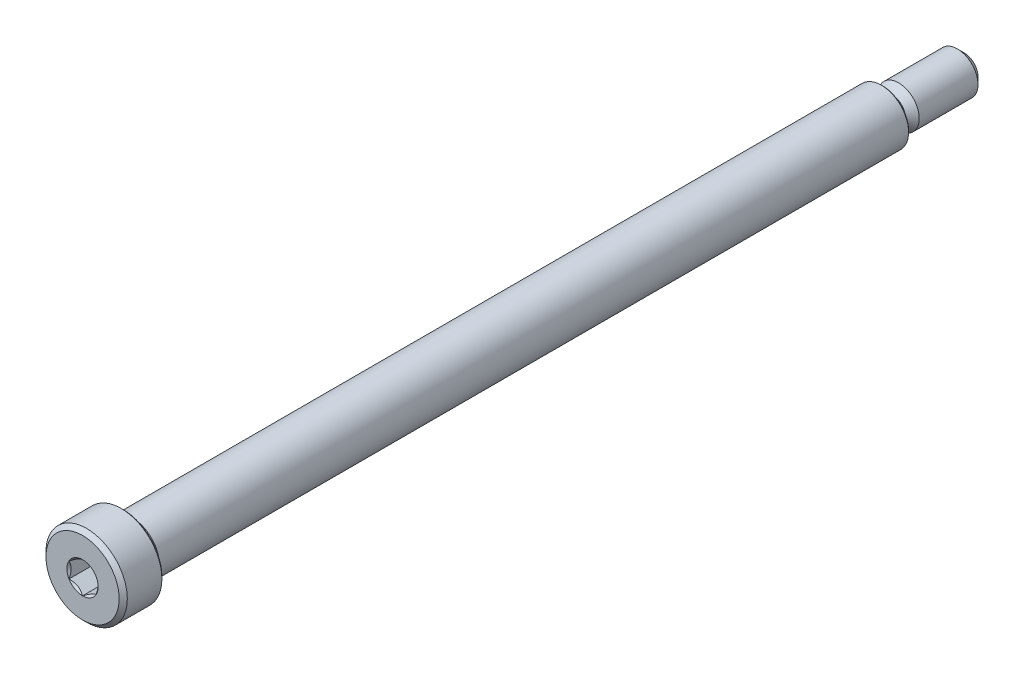
SolidWorks part; units mm, degrees
ref_plane "Front Plane" through (0, 0, 0) normal (0, 0, 1) x (1, 0, 0)
ref_plane "Top Plane" through (0, 0, 0) normal (0, 1, 0) x (1, 0, 0)
ref_plane "Right Plane" through (0, 0, 0) normal (1, 0, 0) x (0, 0, -1)
sketch "Sketch1" plane through (0, 0, 0) normal (0, 0, 1) x (1, 0, 0)
  line L1 (0, 1.8331) -> (-1.5875, 0.9165)
  line L2 (-1.5875, 0.9165) -> (-1.5875, -0.9165)
  line L3 (-1.5875, -0.9165) -> (0, -1.8331)
  line L4 (0, -1.8331) -> (1.5875, -0.9165)
  line L5 (1.5875, -0.9165) -> (1.5875, 0.9165)
  line L6 (1.5875, 0.9165) -> (0, 1.8331)
  circle A0 centre (0, 0) radius 4.7625
  circle A1 centre (0, 0) radius 1.5875 construction
  point P3 (0, 4.7625)
  point P11 (0, -4.7625)
  dimension "Head Diameter" = 9.525
  dimension "Drive Size" = 3.175
sketch "Sketch2" plane through (0, 0, 0) normal (1, 0, 0) x (0, 0, -1)
  line L0 (-51.5937, 0) -> (51.5938, 0) construction
  point P2 (0, 0)
  point P4 (-46.8312, 0)
  point P5 (42.0687, 0)
  point P6 (-46.8312, -3.175)
  point P7 (-48.4981, 0)
  point P8 (50.5354, 0)
  point P9 (50.0062, -2.413)
  point P10 (51.5938, 2.413)
  point P12 (51.5938, -2.413)
  point P15 (-45.7729, -3.175)
  dimension "Head Height" = 4.7625
  dimension "Shoulder Length" = 88.9
  dimension "Thread Length" = 9.525
  dimension "Screw Size Decimal Equivalent" = 4.826
  dimension "Thread Pitch" = 1.0583
  dimension "D1" = 3.0956
  dimension "D2" = 1.5875
  dimension "D3" = 1.0583
  dimension "Shoulder Diameter" = 6.35
sketch "Sketch3" plane through (0, 0, 0) normal (1, 0, 0) x (0, 0, -1)
  line L0 (-51.5937, 0) -> (-51.5937, 4.2862)
  line L1 (-51.1175, 4.7625) -> (-47.0694, 4.7625)
  line L2 (-46.8312, 4.5244) -> (-46.8312, 3.1353)
  line L3 (-46.7122, 3.0162) -> (-45.9317, 3.0162)
  line L4 (-45.7729, 3.0162) -> (-45.7729, 3.175) construction
  line L5 (-45.7729, 3.175) -> (41.91, 3.175)
  line L6 (42.4656, 1.6192) -> (42.4656, 2.413) construction
  line L7 (-51.5937, 0) -> (51.5938, 0)
  line L8 (42.0687, 3.0163) -> (42.0687, 2.0161)
  line L9 (42.4656, 1.6192) -> (43.1271, 1.6192)
  line L10 (43.1271, 1.6192) -> (43.9208, 2.413)
  line L11 (43.9208, 2.413) -> (50.8, 2.413)
  line L12 (50.8, 2.413) -> (51.5938, 1.6192)
  line L13 (51.5938, 1.6192) -> (51.5938, 0)
  line L14 (-51.5937, 4.2862) -> (-51.1175, 4.7625)
  line L15 (-47.0694, 4.7625) -> (-46.8312, 4.5244)
  line L16 (-51.1175, 4.7625) -> (-51.1175, 4.5244) construction
  line L17 (-51.1175, 4.5244) -> (-51.1175, 4.2862) construction
  line L18 (-46.7122, 3.0162) -> (-46.7122, 3.0559) construction
  line L19 (-46.7122, 3.0559) -> (-46.7122, 3.0956) construction
  line L20 (-46.7122, 3.0956) -> (-46.7122, 3.1353) construction
  line L21 (-46.7122, 3.1353) -> (-46.7122, 3.175) construction
  line L22 (-45.7729, 3.175) -> (-45.9317, 3.0162)
  line L23 (41.91, 3.175) -> (42.0687, 3.0163)
  arc A0 (-46.8312, 3.1353) -> (-46.7122, 3.0162) centre (-46.7122, 3.1353) ccw
  arc A1 (42.0687, 2.0161) -> (42.4656, 1.6192) centre (42.4656, 2.0161) ccw
  point P3 (-50.8794, 4.7625)
  point P11 (-48.9744, 4.7625)
  point P35 (42.4656, 2.0161)
  dimension "D1" = 3.175
  dimension "D2" = 3.0162
  dimension "D5" = 2.413
  dimension "D6" = 45
  dimension "D7" = 0.7938
  dimension "D8" = 0.4763
  dimension "D4" = 1.0583
  dimension "D9" = 0.2381
  dimension "D10" = 1.905
revolve "Revolve1" add sketch "Sketch3" angle 360 about L7
sketch "Sketch4" plane through (0, 0, 51.5937) normal (0, 0, 1) x (1, 0, 0)
  line L0 (-1.5875, -0.9165) -> (0, -1.8331) construction
  line L1 (-1.5875, 0.9165) -> (-1.5875, -0.9165) construction
  line L2 (0, 1.8331) -> (-1.5875, 0.9165) construction
  line L3 (1.5875, 0.9165) -> (0, 1.8331) construction
  line L4 (1.5875, -0.9165) -> (1.5875, 0.9165) construction
  line L5 (0, -1.8331) -> (1.5875, -0.9165) construction
  line L6 (-1.5875, -0.9165) -> (0, -1.8331)
  line L7 (-1.5875, 0.9165) -> (-1.5875, -0.9165)
  line L8 (0, 1.8331) -> (-1.5875, 0.9165)
  line L9 (1.5875, 0.9165) -> (0, 1.8331)
  line L10 (1.5875, -0.9165) -> (1.5875, 0.9165)
  line L11 (0, -1.8331) -> (1.5875, -0.9165)
extrude "Cut-Extrude1" cut sketch "Sketch4" against normal up to vertex (3.0956 mm away) up to point (0, 0, 48.4981)
sketch "Sketch5" plane through (0, 0, 51.5937) normal (0, 0, 1) x (1, 0, 0)
  circle A0 centre (0, 0) radius 1.8331
extrude "Cut-Extrude2" cut sketch "Sketch5" against normal up to vertex (3.0956 mm away) draft 45 up to point (0, 0, 48.4981)
ref_plane "Plane1" [suppressed] through (0, 0, -43.1271) normal (0, 0, 1) x (1, 0, 0)
split "Split1" [suppressed] bodies to split 106
sketch "Sketch6" [suppressed] plane through (0, 0, -51.5938) normal (0, 0, -1) x (-1, 0, 0)
  circle A0 centre (0, 0) radius 2.413 construction
  circle A1 centre (0, 0) radius 2.413
curve "Helix/Spiral1" [suppressed] pitch 1.0583 height 9.525 turns 9
sketch "Sketch7" [suppressed] plane through (0, 0, 0) normal (1, 0, 0) x (0, 0, -1)
  line L0 (51.5276, 2.5276) -> (52.0568, 1.611) construction
  line L1 (52.0568, 1.611) -> (52.5859, 2.5276) construction
  line L2 (52.5859, 2.5276) -> (51.5276, 2.5276) construction
  line L3 (51.5607, 2.4703) -> (52.5529, 2.4703)
  line L4 (52.5529, 2.4703) -> (52.1229, 1.7256)
  line L5 (52.1229, 1.7256) -> (51.9906, 1.7256)
  line L6 (51.9906, 1.7256) -> (51.5607, 2.4703)
  line L7 (52.0568, 1.7256) -> (52.0568, 1.611) construction
  line L8 (51.5938, 2.413) -> (52.5198, 2.413) construction
  line L9 (52.0568, 2.5276) -> (52.0568, 2.413) construction
  point P12 (52.0568, 2.4703)
  dimension "D1" = 1.0583
  dimension "D2" = 0.1323
sweep "Cut-Sweep1" [suppressed] cut profiles "Sketch7" path "Helix/Spiral1"
combine bodies "Combine1" [suppressed] operation type add bodies to combine 109 108
sketch "Sketch8" [suppressed] plane through (0, 0, 51.5937) normal (0, 0, 1) x (1, 0, 0)
  line L0 (0, 0) -> (0, 4.7625) construction
  line L1 (-0.1247, 4.7625) -> (0.1247, 4.7625)
  line L2 (0, 0) -> (-0.1247, 4.7625) construction
  line L3 (0.1247, 4.7625) -> (0, 0) construction
  line L4 (-0.1247, 4.7625) -> (0, 4.5465)
  line L5 (0, 4.5465) -> (0.1247, 4.7625)
  circle A0 centre (0, 0) radius 4.7625 construction
  point P7 (0, 4.7625)
  dimension "D1" = 1.5
extrude "Cut-Extrude3" [suppressed] cut sketch "Sketch8" against normal up to vertex from vertex
pattern_circular "CirPattern1" [suppressed] count 96 over 360 about axis through (0, 0, 51.5937) along (0, 0, -1) of bodies 111
equation "\"D1@Sketch2\"=0.65*\"Head Height@Sketch2\""
equation "\"D2@Sketch2\"=\"Thread Pitch@Sketch2\"*1.5"
equation "\"D1@Sketch3\"=0.5*\"Shoulder Diameter@Sketch2\""
equation "\"D2@Sketch3\"=0.95*\"D1@Sketch3\""
equation "\"D5@Sketch3\"=0.5*\"Screw Size Decimal Equivalent@Sketch2\""
equation "\"D7@Sketch3\"=0.75*\"Thread Pitch@Sketch2\""
equation "\"D8@Sketch3\"=0.05*\"Head Diameter@Sketch1\""
equation "\"D4@Sketch3\"=\"Thread Pitch@Sketch2\""
equation "\"D4@Helix/Spiral1\"=\"Thread Pitch@Sketch2\""
equation "\"D3@Helix/Spiral1\"=\"Thread Length@Sketch2\""
equation "\"D2@Sketch7\"=\"D1@Sketch7\"/8"
equation "\"D1@Sketch7\"=\"Thread Pitch@Sketch2\""
equation "\"D9@Sketch3\"=.05*\"Head Height@Sketch2\""
equation "\"D10@Sketch3\"=.4*\"Head Height@Sketch2\""
equation "\"D1@CirPattern1\"=360/(2*\"D1@Sketch8\"*1.25)"
equation "\"D3@Sketch2\"=\"Thread Pitch@Sketch2\""
